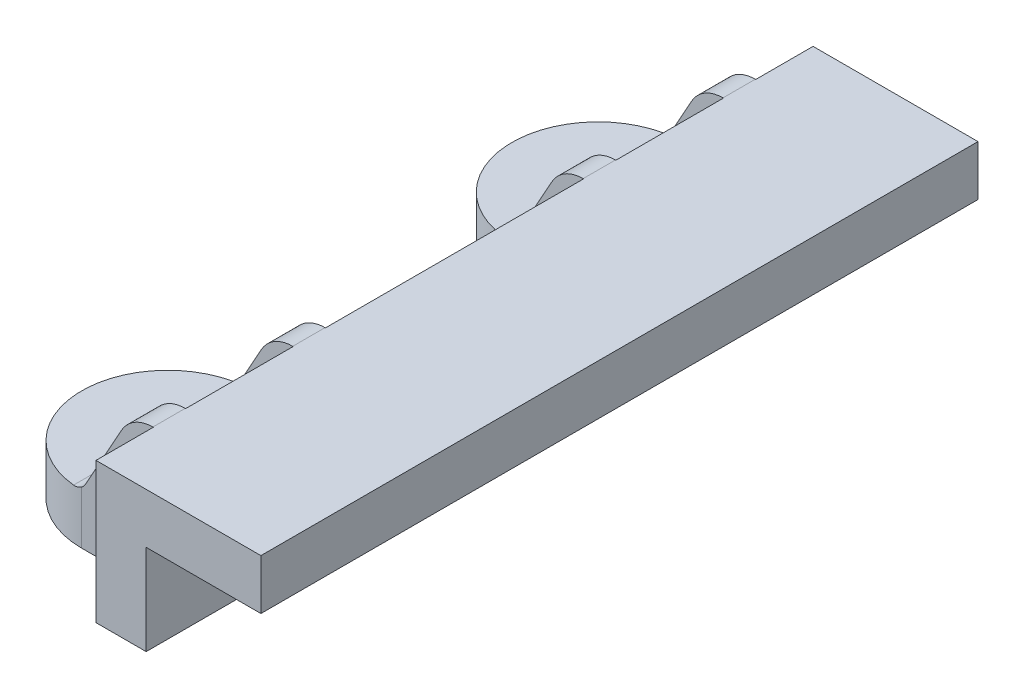
SolidWorks part; units mm, degrees
ref_plane "Alzado" through (0, 0, 0) normal (0, 0, 1) x (1, 0, 0)
ref_plane "Planta" through (0, 0, 0) normal (0, 1, 0) x (1, 0, 0)
ref_plane "Vista lateral" through (0, 0, 0) normal (1, 0, 0) x (0, 0, -1)
sketch "Croquis1" plane through (0, 0, 0) normal (0, 0, 1) x (1, 0, 0)
  line L0 (0, 0) -> (0, 9.8)
  line L1 (0, 9.8) -> (11.5, 9.8)
  line L2 (11.5, 9.8) -> (11.5, 6.3)
  line L3 (11.5, 6.3) -> (3.5, 6.3)
  line L4 (3.5, 6.3) -> (3.5, 0)
  line L5 (3.5, 0) -> (0, 0)
  dimension "D1" = 3.5
  dimension "D2" = 8
  dimension "D3" = 3.5
  dimension "D4" = 6.3
extrude "Saliente-Extruir1" add sketch "Croquis1" along normal mid plane 50
sketch "Croquis2" plane through (0, 0, 0) normal (0, 1, 0) x (1, 0, 0)
  line L0 (0, -25) -> (0, 25) construction
  line L1 (0, 9) -> (-5, 9)
  line L2 (0, 9) -> (0, 21)
  line L3 (0, 21) -> (-5, 21)
  line L5 (11.5, 25) -> (0, 25) construction
  arc A0 (-5, 21) -> (-5, 9) centre (-5, 15) ccw
  circle A1 centre (-5, 15) radius 2.25
  point P6 (0, 15)
  dimension "D4" = 4.5
  dimension "D1" = 10
  dimension "D2" = 12
  dimension "D3" = 5
extrude "Saliente-Extruir2" add sketch "Croquis2" along normal blind 3.5
sketch "Croquis3" plane through (0, 0, -9) normal (0, 0, 1) x (1, 0, 0)
  line L1 (0, 9.8) -> (0, 3.5)
  line L2 (0, 9.8) -> (0, 0) construction
  line L3 (-5, 3.5) -> (0, 3.5) construction
  line L4 (0, 3.5) -> (-5, 3.5)
  line L5 (-5, 3.5) -> (-1.5, 9.8)
  line L6 (-1.5, 9.8) -> (0, 9.8)
  dimension "D1" = 1.5
extrude "Saliente-Extruir3" add sketch "Croquis3" against normal blind 2.25
fillet "Redondeo3" radius 1 1 edges at (-5, 3.5, -10.125)
fillet "Redondeo5" radius 2.5 1 edges at (-1.5, 9.8, -10.125)
ref_plane "Plano1" through (0, 0, -15) normal (0, 0, -1) x (-1, 0, 0)
mirror "Simetría1" about plane through (0, 0, -15) normal (0, 0, -1) of "Saliente-Extruir3", "Redondeo3", "Redondeo5"
mirror "Simetría4" about plane through (0, 0, 0) normal (0, 0, 1) of "Saliente-Extruir2", "Saliente-Extruir3", "Redondeo3", "Redondeo5"
ref_plane "Plano2" through (0, 0, 15) normal (0, 0, -1) x (-1, 0, 0)
sketch "Croquis4" plane through (0, 0, 21) normal (0, 0, 1) x (1, 0, 0)
  line L0 (0, 3.5) -> (-5, 3.5)
  line L1 (-5, 3.5) -> (-1.5, 9.8)
  line L2 (0, 9.8) -> (-1.5, 9.8)
  line L4 (0, 3.5) -> (0, 9.8)
  point P4 (-1.5, 9.8)
  point P7 (-1.5, 9.8)
  point P8 (0, 0)
  dimension "D1" = 1.5
extrude "Saliente-Extruir4" add sketch "Croquis4" against normal blind 2.25
fillet "Redondeo6" radius 2.5 1 edges at (-1.5, 9.8, 19.875)
fillet "Redondeo7" radius 1 1 edges at (-5, 3.5, 19.875)
